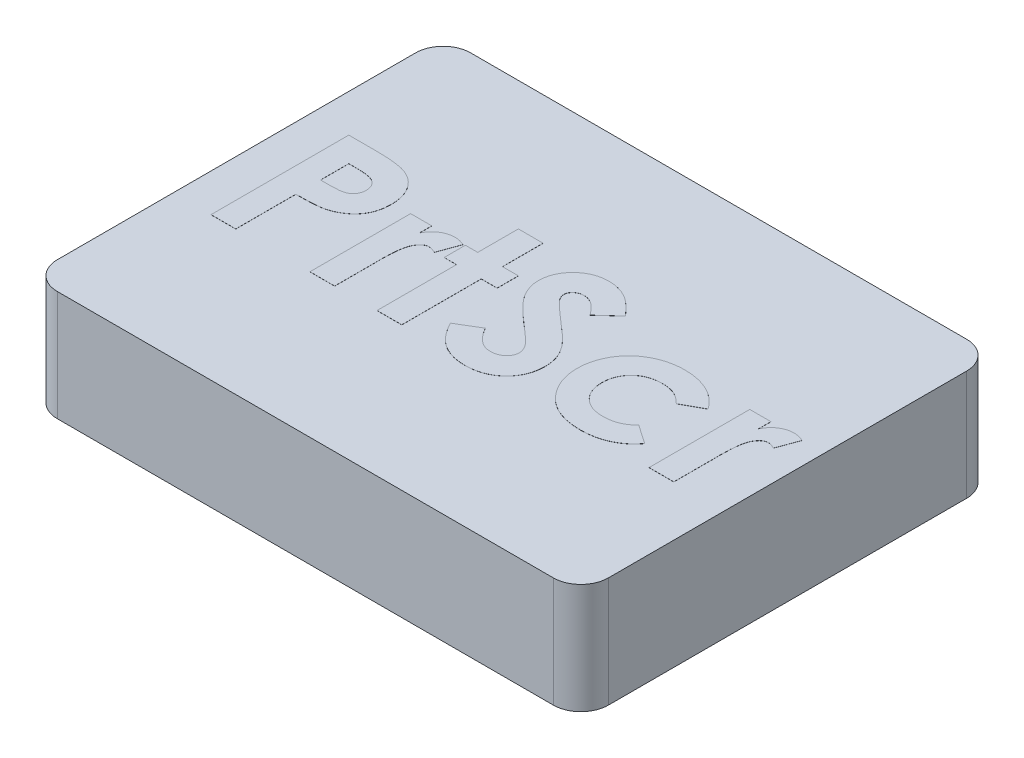
SolidWorks part; units mm, degrees
ref_plane "Front Plane" through (0, 0, 0) normal (0, 0, 1) x (1, 0, 0)
ref_plane "Top Plane" through (0, 0, 0) normal (0, 1, 0) x (1, 0, 0)
ref_plane "Right Plane" through (0, 0, 0) normal (1, 0, 0) x (0, 0, -1)
sketch "Sketch1" plane through (0, 0, 0) normal (0, 1, 0) x (1, 0, 0)
  line L0 (0, 0) -> (12.7, 0)
  line L1 (12.7, 0) -> (12.7, 9.525)
  line L2 (12.7, 9.525) -> (0, 9.525)
  line L3 (0, 9.525) -> (0, 0)
  dimension "D1" = 12.7
  dimension "D2" = 9.525
extrude "Boss-Extrude1" add sketch "Sketch1" along normal blind 2.54
fillet "Fillet1" radius 0.635 4 edges at (0, 1.27, -9.525) (12.7, 1.27, -9.525) (12.7, 1.27, 0) (0, 1.27, 0)
shell "Shell1" thickness 0.635 removed face at (6.35, 0, -4.7625)
sketch "Sketch2" plane through (0, 1.905, 0) normal (0, -1, 0) x (-1, 0, 0)
  line L0 (-0.635, 4.7625) -> (-12.065, 4.7625) construction
  line L1 (-0.635, 8.89) -> (-0.635, 0.635) construction
  line L2 (-12.065, 0.635) -> (-12.065, 8.89) construction
  line L3 (-6.35, 0.635) -> (-6.35, 8.89) construction
  line L4 (-0.635, 0.635) -> (-12.065, 0.635) construction
  line L5 (-12.065, 8.89) -> (-0.635, 8.89) construction
  circle A0 centre (-6.35, 4.7625) radius 2.54
  dimension "D1" = 5.08
extrude "Boss-Extrude2" add sketch "Sketch2" along normal up to surface (1.905 mm away) up to face at (6.35, 0, -4.7625)
sketch "Sketch3" plane through (0, 2.54, 0) normal (0, 1, 0) x (1, 0, 0)
  line L0 (0.635, 0) -> (12.065, 0) construction
  line L1 (0, 8.89) -> (0, 0.635) construction
  text T0 "<b>PrtScr</b>"
  dimension "D1" = 3.302
  dimension "D2" = 0.508
extrude "Boss-Extrude3" add sketch "Sketch3" along normal blind 0.0025
